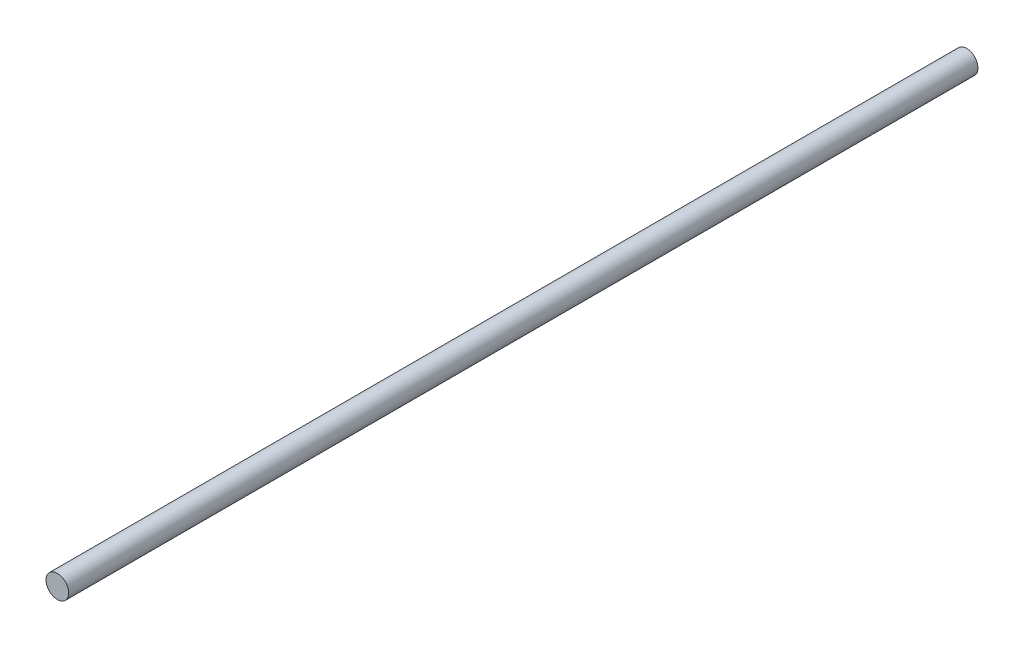
SolidWorks part; units mm, degrees
material "AISI Type 316L stainless steel"
ref_plane "Front Plane" through (0, 0, 0) normal (0, 0, 1) x (1, 0, 0)
ref_plane "Top Plane" through (0, 0, 0) normal (0, 1, 0) x (1, 0, 0)
ref_plane "Right Plane" through (0, 0, 0) normal (1, 0, 0) x (0, 0, -1)
sketch "Sketch1" plane through (0, 0, 0) normal (0, 0, 1) x (1, 0, 0)
  circle A0 centre (0, 0) radius 1.25
  dimension "D1" = 2.5
extrude "Boss-Extrude1" add sketch "Sketch1" along normal mid plane 100
